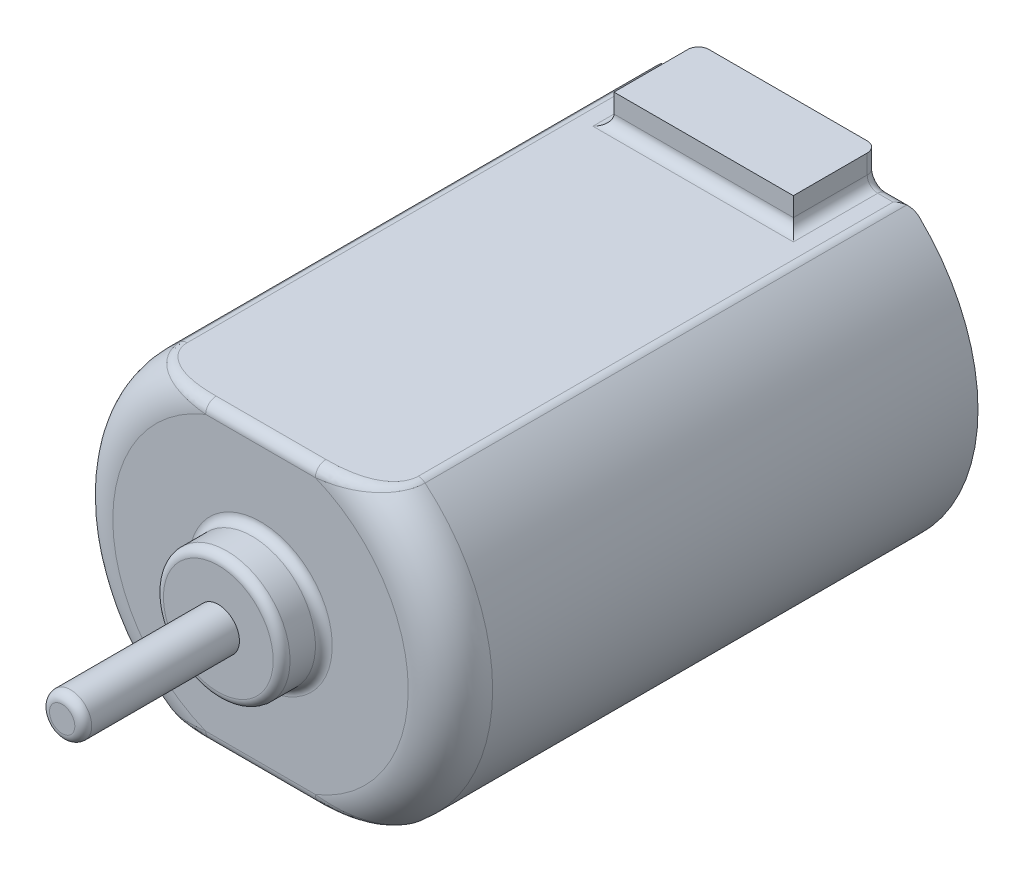
SolidWorks part; units mm, degrees
ref_plane "Front Plane" through (0, 0, 0) normal (0, 0, 1) x (1, 0, 0)
ref_plane "Top Plane" through (0, 0, 0) normal (0, 1, 0) x (1, 0, 0)
ref_plane "Right Plane" through (0, 0, 0) normal (1, 0, 0) x (0, 0, -1)
sketch "Sketch1" plane through (0, 0, 0) normal (0, 0, 1) x (1, 0, 0)
  line L0 (-5.6569, 14) -> (5.6569, 14)
  line L1 (5.6569, 0) -> (-5.6569, 0)
  line L2 (0, 0) -> (0, 14) construction
  line L3 (-5.6569, 14) -> (-5.6569, 0) construction
  arc A0 (5.6569, 14) -> (5.6569, 0) centre (0, 7) cw
  arc A1 (-5.6569, 14) -> (-5.6569, 0) centre (0, 7) ccw
  dimension "D2" = 9
  dimension "D1" = 14
extrude "Boss-Extrude1" add sketch "Sketch1" against normal blind 25
sketch "Sketch2" plane through (0, 0, 0) normal (0, 0, 1) x (1, 0, 0)
  circle A0 centre (0, 7) radius 3
  arc A1 (5.6569, 0) -> (5.6569, 14) centre (0, 7) ccw construction
  dimension "D1" = 6
extrude "Boss-Extrude2" add sketch "Sketch2" along normal blind 2
sketch "Sketch3" plane through (0, 0, 2) normal (0, 0, 1) x (1, 0, 0)
  circle A0 centre (0, 7) radius 1
  circle A1 centre (0, 7) radius 3 construction
  dimension "D1" = 2
extrude "Boss-Extrude3" add sketch "Sketch3" along normal offset from surface (7.4 mm away) 9.4 up to face at (0, 7, 0) offset beyond the face yes
sketch "Sketch4" plane through (0, 0, -25) normal (0, 0, -1) x (-1, 0, 0)
  line L0 (-3, 3) -> (3, 3)
  arc A0 (3, 3) -> (-3, 3) centre (0, 7) ccw
  arc A1 (5.6569, 0) -> (5.6569, 14) centre (0, 7) ccw construction
  dimension "D2" = 5
  dimension "D1" = 4
extrude "Boss-Extrude4" add sketch "Sketch4" along normal blind 2.3
sketch "Sketch5" plane through (0, 0, -25) normal (0, 0, -1) x (-1, 0, 0)
  line L0 (-5.6569, 14) -> (5.6569, 14) construction
  line L1 (-4.25, 14) -> (4.25, 14)
  line L2 (-4.25, 14) -> (-4.25, 15.4)
  line L3 (-4.25, 15.4) -> (4.25, 15.4)
  line L4 (4.25, 14) -> (4.25, 15.4)
  line L5 (0, 0) -> (0, 21.936) construction
  dimension "D1" = 8.5
  dimension "D2" = 1.4
extrude "Boss-Extrude5" add sketch "Sketch5" against normal blind 4
sketch "Sketch6" plane through (0, 0, -27.3) normal (0, 0, -1) x (-1, 0, 0)
  circle A0 centre (0, 7) radius 1
  arc A1 (3, 3) -> (-3, 3) centre (0, 7) ccw construction
  dimension "D1" = 2
extrude "Boss-Extrude6" add sketch "Sketch6" along normal offset from surface (1.3 mm away) 38 up to face at (-1, 7, 9.4)
fillet "Fillet1" radius 2 2 edges at (-9, 7, 0) (9, 7, 0)
fillet "Fillet2" radius 0.5 16 edges at (0, 14, -21) (5.6569, 14, -13.5) (5.2495, 14, -1.0312) (-5.3173, 14, -1.1089) (-5.6569, 14, -13.5) (5.3173, 0, -1.1089) (5.6569, 0, -13.5) (0, 0, -25) (-5.6569, 0, -13.5) (-5.2495, 0, -1.0312)
fillet "Fillet4" radius 0.4 6 edges at (-3, 7, 0) (3, 7, 2) (0, 3, -27.3) (0, 3, -25) (0, 12, -25) (0, 12, -27.3)
fillet "Fillet5" radius 0.4 2 edges at (-1, 7, -28.6) (-1, 7, 9.4)
